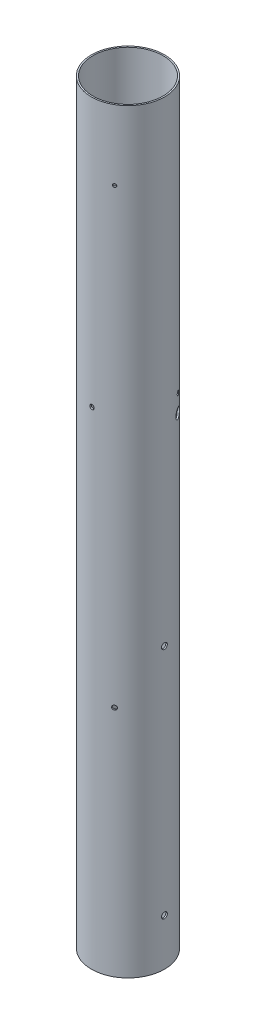
SolidWorks part; units mm, degrees
material "G10 Fiberglass"
ref_plane "Front Plane" through (0, 0, 0) normal (0, 0, 1) x (1, 0, 0)
ref_plane "Top Plane" through (0, 0, 0) normal (0, 1, 0) x (1, 0, 0)
ref_plane "Right Plane" through (0, 0, 0) normal (1, 0, 0) x (0, 0, -1)
sketch "Sketch1" plane through (0, 0, 0) normal (0, 1, 0) x (1, 0, 0)
  circle A0 centre (0, 0) radius 38.1635
  circle A1 centre (0, 0) radius 39.7891
  dimension "D1" = 76.327
  dimension "D2" = 1.6256
extrude "Boss-Extrude1" add sketch "Sketch1" along normal blind 822.5282
ref_axis "Axis1" through (0, -40.64, 0) along (0, 1, 0)
ref_plane "Plane1" through (19.8945, 0, 34.4584) normal (0.5, 0, 0.866) x (0, -1, 0)
sketch "Sketch2" plane through (19.8945, 0, 34.4584) normal (0.5, 0, 0.866) x (0, -1, 0)
  line L0 (40.64, 0) -> (-853.44, 0) construction
  line L1 (-822.5282, 38.1635) -> (-822.5282, -38.1635) construction
  line L2 (-822.5282, 38.1635) -> (-822.5282, -38.1635) construction
  circle A0 centre (-746.3282, 0) radius 1.778
  dimension "D1" = 76.2
  dimension "D2" = 3.556
extrude "Cut-Extrude1" cut sketch "Sketch2" against normal up to next
pattern_circular "CirPattern1" count 3 over 360 about axis through (0, -40.64, 0) along (0, 1, 0) of "Cut-Extrude1"
ref_plane "Plane2" through (39.7891, 0, 0) normal (1, 0, 0) x (0, 0, -1)
sketch "Sketch3" plane through (39.7891, 0, 0) normal (1, 0, 0) x (0, 0, -1)
  line L0 (0, -40.64) -> (0, 853.44) construction
  circle A0 centre (0, 50.8) radius 3.175
  circle A1 centre (0, 304.8) radius 3.175
  dimension "D1" = 6.35
  dimension "D2" = 6.35
  dimension "D3" = 50.8
  dimension "D4" = 254
extrude "Cut-Extrude2" cut sketch "Sketch3" against normal up to next
ref_plane "Plane3" through (0, 530.4282, 0) normal (0, 1, 0) x (1, 0, 0)
ref_axis "Axis2" through (18.2248, 746.3282, 31.5663) along (0.5, 0, 0.866)
ref_plane "Plane4" through (-34.7362, 0, -19.4054) normal (-0.873, 0, -0.4877) x (0, -1, 0)
sketch "Sketch4" plane through (-34.7362, 0, -19.4054) normal (-0.873, 0, -0.4877) x (0, -1, 0)
  line L0 (-530.4282, 43.768) -> (-530.4282, -43.768) construction
  line L1 (40.64, 0) -> (-853.44, 0) construction
  circle A0 centre (-530.4282, 0) radius 2.3812
  dimension "D1" = 4.7625
extrude "Cut-Extrude3" cut sketch "Sketch4" against normal up to next
pattern_circular "CirPattern2" count 3 over 360 about axis through (0, -40.64, 0) along (0, 1, 0) of "Cut-Extrude3"
ref_plane "Plane5" through (0, 511.3782, 0) normal (0, 1, 0) x (1, 0, 0)
ref_plane "Plane6" through (34.1737, 0, -20.3797) normal (0.8589, 0, -0.5122) x (0, -1, 0)
sketch "Sketch6" plane through (34.1737, 0, -20.3797) normal (0.8589, 0, -0.5122) x (0, -1, 0)
  line L0 (-511.3782, 43.768) -> (-511.3782, -43.768) construction
  line L1 (40.64, 0) -> (-853.44, 0) construction
  circle A0 centre (-511.3782, 0) radius 5.5563
  dimension "D1" = 11.1125
extrude "Cut-Extrude4" cut sketch "Sketch6" against normal up to next
ref_plane "Plane7" through (0, 254, 0) normal (0, 1, 0) x (1, 0, 0)
ref_plane "Plane8" through (19.8945, 0, 34.4584) normal (0.5, 0, 0.866) x (0, -1, 0)
sketch "Sketch7" plane through (19.8945, 0, 34.4584) normal (0.5, 0, 0.866) x (0, -1, 0)
  line L0 (-254, 43.768) -> (-254, -43.768) construction
  circle A0 centre (-254, 0) radius 2.3813
  dimension "D1" = 4.7625
extrude "Cut-Extrude5" cut sketch "Sketch7" against normal up to next
pattern_circular "CirPattern3" count 3 over 360 about axis through (0, -40.64, 0) along (0, 1, 0) of "Cut-Extrude5"
equation "\"D2@Sketch3\"=\"D1@Sketch3\""
